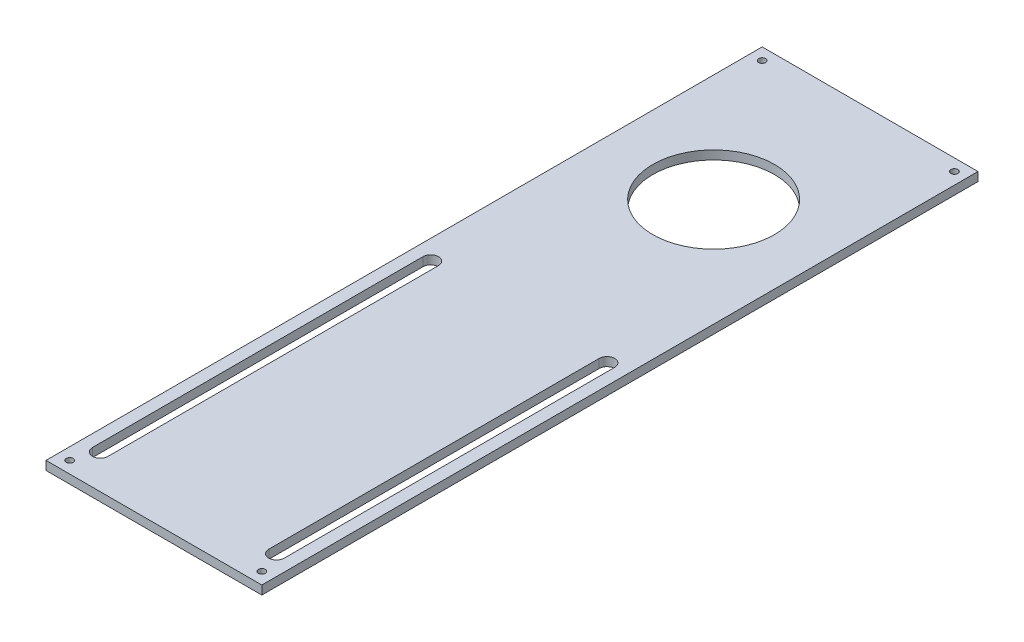
SolidWorks part; units mm, degrees
material "Brass"
ref_plane "Front Plane" through (0, 0, 0) normal (0, 0, 1) x (1, 0, 0)
ref_plane "Top Plane" through (0, 0, 0) normal (0, 1, 0) x (1, 0, 0)
ref_plane "Right Plane" through (0, 0, 0) normal (1, 0, 0) x (0, 0, -1)
sketch "Sketch2" plane through (0, 0, 0) normal (0, 0, 1) x (1, 0, 0)
  line L0 (-44.45, 0) -> (-44.45, -3.2004)
  line L1 (0, 0) -> (0, -3.2004) construction
  line L2 (-44.45, -3.2004) -> (34.3945, -3.2004)
  line L3 (34.3945, 0) -> (34.3945, -3.2004)
  line L4 (-44.45, 0) -> (34.3945, 0)
  dimension "D1" = 78.8445
  dimension "D2" = 3.2004
extrude "Boss-Extrude1" add sketch "Sketch2" along normal blind 261.62 contours L4 L3 L2 L0
sketch "Sketch3" plane through (0, -3.2004, 0) normal (0, -1, 0) x (1, 0, 0)
  line L0 (-44.45, 57.15) -> (34.3945, 57.15) construction
  line L1 (30.0765, 261.62) -> (30.0765, 257.302) construction
  line L2 (30.0765, 257.302) -> (34.3945, 257.302) construction
  line L3 (-44.45, 261.62) -> (34.3945, 261.62) construction
  line L4 (-5.0278, 57.15) -> (-5.0278, 0) construction
  line L5 (-44.45, 0) -> (34.3945, 0) construction
  line L6 (-40.0535, 128.3174) -> (-34.3859, 128.3174) construction
  line L7 (-40.0535, 128.3174) -> (-40.0535, 249.024)
  line L8 (-40.0535, 249.024) -> (-34.3859, 249.024) construction
  line L9 (-34.3859, 128.3174) -> (-34.3859, 249.024)
  line L10 (-37.2197, 261.62) -> (-37.2197, 251.8579) construction
  line L11 (-40.0535, 188.6707) -> (-44.45, 188.6707) construction
  line L12 (24.3303, 128.3174) -> (29.998, 128.3174) construction
  line L13 (24.3303, 128.3174) -> (24.3303, 249.024)
  line L14 (24.3303, 249.024) -> (29.998, 249.024) construction
  line L15 (29.998, 128.3174) -> (29.998, 249.024)
  line L16 (27.1642, 261.62) -> (27.1642, 251.8579) construction
  line L17 (34.3945, 188.6707) -> (29.998, 188.6707) construction
  line L18 (34.3945, 261.62) -> (34.3945, 0) construction
  line L19 (-44.45, 4.318) -> (-40.132, 4.318) construction
  line L20 (34.3945, 261.62) -> (34.3945, 0) construction
  line L21 (-44.45, 261.62) -> (-44.45, 0) construction
  line L22 (-44.45, 261.62) -> (-44.45, 0) construction
  line L23 (-40.132, 261.62) -> (-40.132, 257.302) construction
  line L24 (-44.45, 257.302) -> (-40.132, 257.302) construction
  line L25 (-44.45, 261.62) -> (34.3945, 261.62) construction
  line L26 (-40.132, 4.318) -> (-40.132, 0) construction
  line L27 (-44.45, 0) -> (34.3945, 0) construction
  line L28 (34.3945, 4.318) -> (30.0765, 4.318) construction
  line L29 (30.0765, 0) -> (30.0765, 4.318) construction
  circle A0 centre (-5.0278, 57.15) radius 22.225
  arc A1 (-40.0535, 249.024) -> (-34.3859, 249.024) centre (-37.2197, 249.024) cw
  arc A2 (-34.3859, 128.3174) -> (-40.0535, 128.3174) centre (-37.2197, 128.3174) cw
  arc A3 (24.3303, 249.024) -> (29.998, 249.024) centre (27.1642, 249.024) cw
  arc A4 (29.998, 128.3174) -> (24.3303, 128.3174) centre (27.1642, 128.3174) cw
  circle A5 centre (-40.132, 257.302) radius 1.27
  circle A6 centre (30.0765, 257.302) radius 1.27
  circle A7 centre (-40.132, 4.318) radius 1.27
  circle A8 centre (30.0765, 4.318) radius 1.27
  dimension "D1" = 44.45
  dimension "D11" = 2.54
  dimension "D2" = 57.15
  dimension "D3" = 120.7066
  dimension "D4" = 5.6676
  dimension "D5" = 9.7621
  dimension "D6" = 4.3965
  dimension "D7" = 120.7066
  dimension "D8" = 5.6676
  dimension "D9" = 9.7621
  dimension "D10" = 4.3965
  dimension "D12" = 4.318
extrude "Cut-Extrude1" cut sketch "Sketch3" against normal through all
